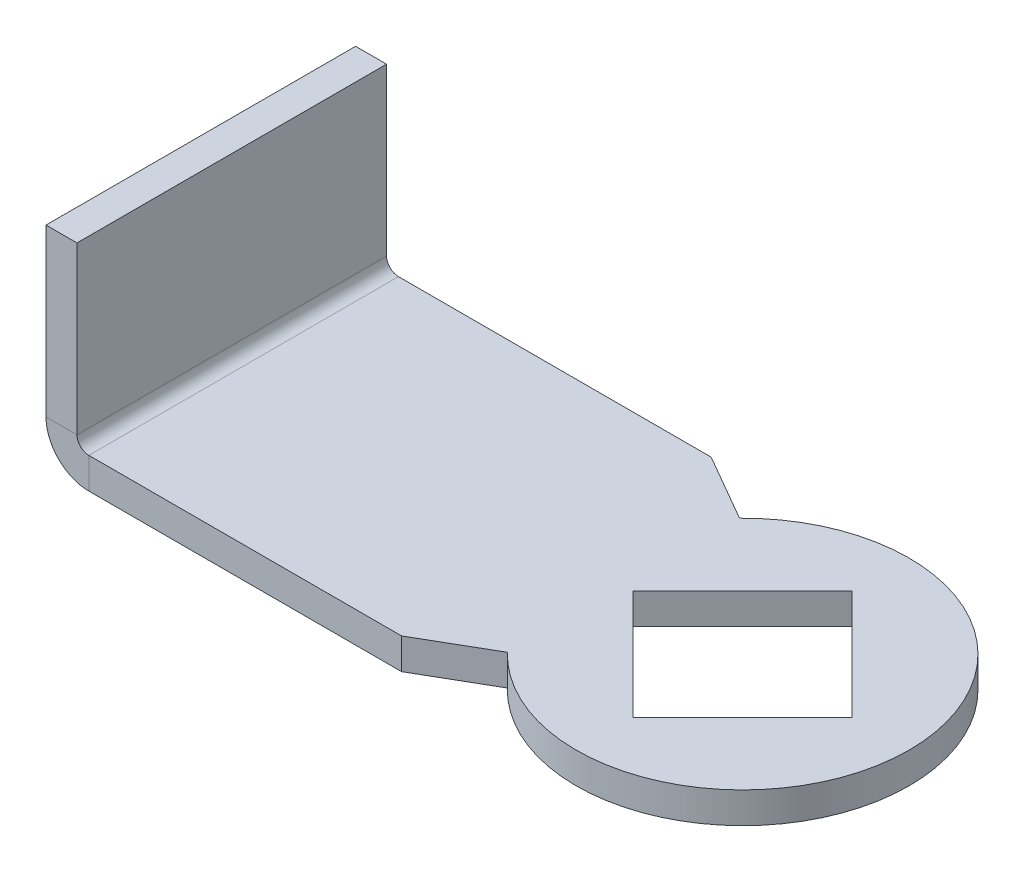
SolidWorks part; units mm, degrees
note: The reader was unsure of these and kept them because the rebuilt part matched: thickness of "基体-法兰1", "边线-法兰1", "钣金9", "钣金10", "钣金11"; flange length of "边线-法兰1".
ref_plane "前视基准面" through (0, 0, 0) normal (0, 0, 1) x (1, 0, 0)
ref_plane "上视基准面" through (0, 0, 0) normal (0, 1, 0) x (1, 0, 0)
ref_plane "右视基准面" through (0, 0, 0) normal (1, 0, 0) x (0, 0, -1)
sketch "草图2" plane through (0, 0, 0) normal (0, 1, 0) x (1, 0, 0)
  line L0 (-30.0316, -10) -> (-25.7015, -7.5)
  line L1 (-53, 10) -> (-30.0316, 10)
  line L2 (-53, 10) -> (-53, -10)
  line L3 (-53, -10) -> (-30.0316, -10)
  line L4 (-59.6233, 0) -> (20.4513, 0) construction
  line L5 (-30.0316, 10) -> (-25.7015, 7.5)
  arc A0 (-25.7015, -7.5) -> (-25.7015, 7.5) centre (-18, 0) ccw
  dimension "D3" = 30
  dimension "D4" = 21.5
  dimension "D5" = 5
  dimension "D1" = 35
  dimension "D2" = 20
base flange "基体-法兰1" sketch "草图2" thickness 2 reverse thickness direction no parameters "D1"=0.7666
edge flange "边线-法兰1" sketch "草图9" flange angle 90 flange length 13.5 flange position material inside bend radius 0.7666 thickness 2 relief rectangular parameters "D6"=10
sketch "草图9" plane through (-53, 0, 0) normal (-1, 0, 0) x (0, 0, 1)
  line L0 (-10, 0) -> (10, 0) construction
  line L1 (-10, 0) -> (10, 0)
  line L2 (-10, 0) -> (-10, 11.5)
  line L3 (-10, 11.5) -> (10, 11.5)
  line L4 (10, 11.5) -> (10, 0)
bend "边线折弯1" bend radius 0.7666 bend angle 90 parameters "D5"=1
sketch "草图10" plane through (0, -2, -2) normal (0, 1, 0) x (1, 0, 0)
  line L0 (-18, -2) -> (-18, 13.5966) construction
  line L1 (-18, 5.0711) -> (-25.0711, -2)
  line L2 (-25.0711, -2) -> (-18, -9.0711)
  line L3 (-18, -9.0711) -> (-10.9289, -2)
  line L4 (-10.9289, -2) -> (-18, 5.0711)
  circle A0 centre (-18, -2) radius 5 construction
  dimension "D1" = 10
extrude "切除-拉伸1" cut sketch "草图10" along normal through all normal cut yes
sketch "折弯-线1" plane through (0, 0, 0) normal (0, 1, 0) x (1, 0, 0)
sketch "边界框1" plane through (0, 0, 0) normal (0, 1, 0) x (1, 0, 0)
sheet metal parameters "钣金9" thickness 2 parameters "D1"=0.7666, "D7"=3
flat pattern "平板型式9" [suppressed]
sketch "折弯-线2" plane through (0, 0, 0) normal (0, 1, 0) x (1, 0, 0)
sketch "边界框2" [suppressed] plane through (0, 0, 0) normal (0, 1, 0) x (1, 0, 0)
sheet metal parameters "钣金10" thickness 2 parameters "D1"=0.7666, "D7"=3
flat pattern "平板型式9" [suppressed]
sketch "折弯-线2" plane through (0, 0, 0) normal (0, 1, 0) x (1, 0, 0)
sketch "边界框2" [suppressed] plane through (0, 0, 0) normal (0, 1, 0) x (1, 0, 0)
bend of the flat pattern "展开-<边线折弯1>1"
sheet metal parameters "钣金11" thickness 2 parameters "D1"=0.7666, "D7"=3
flat pattern "平板型式9" [suppressed]
sketch "折弯-线2" plane through (0, 0, 0) normal (0, 1, 0) x (1, 0, 0)
sketch "边界框2" [suppressed] plane through (0, 0, 0) normal (0, 1, 0) x (1, 0, 0)
bend of the flat pattern "展开-<边线折弯1>1"
